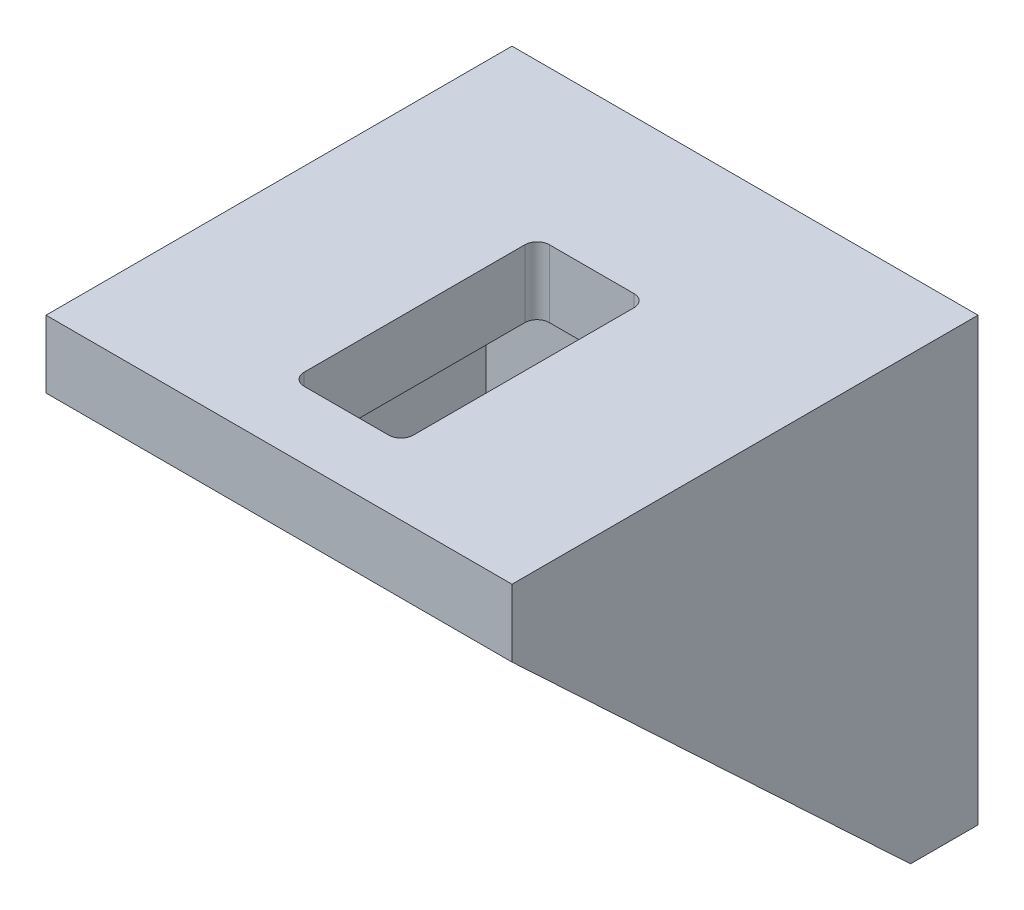
SolidWorks part; units mm, degrees
ref_plane "Front Plane" through (0, 0, 0) normal (0, 0, 1) x (1, 0, 0)
ref_plane "Top Plane" through (0, 0, 0) normal (0, 1, 0) x (1, 0, 0)
ref_plane "Right Plane" through (0, 0, 0) normal (1, 0, 0) x (0, 0, -1)
sketch "Sketch1" plane through (0, 0, 0) normal (0, 0, 1) x (1, 0, 0)
  line L1 (0, 0) -> (38, 0)
  line L2 (0, 0) -> (0, 36)
  line L3 (0, 36) -> (38, 36)
  line L4 (38, 0) -> (38, 36)
  dimension "D1" = 38
  dimension "D2" = 36
extrude "Boss-Extrude1" add sketch "Sketch1" along normal blind 5.5
sketch "Sketch5" plane through (0, 0, 5.5) normal (0, 0, 1) x (1, 0, 0)
  line L0 (38, 0) -> (38, 36) construction
  line L1 (0, 36) -> (38, 36)
  line L2 (0, 36) -> (0, 30.5)
  line L3 (0, 30.5) -> (38, 30.5)
  line L4 (38, 36) -> (38, 30.5)
  dimension "D1" = 5.5
extrude "Boss-Extrude5" add sketch "Sketch5" along normal blind 32.5
sketch "Sketch7" plane through (0, 0, 0) normal (-1, 0, 0) x (0, 0, 1)
  line L0 (5.5, 0) -> (38, 30.5)
  line L1 (38, 30.5) -> (5.5, 30.5)
  line L2 (5.5, 30.5) -> (5.5, 0)
extrude "Boss-Extrude6" add sketch "Sketch7" against normal blind 3.4
sketch "Sketch8" plane through (38, 0, 0) normal (1, 0, 0) x (0, 0, -1)
  line L0 (-5.5, 0) -> (-5.5, 30.5)
  line L1 (-5.5, 30.5) -> (-38, 30.5)
  line L2 (-38, 30.5) -> (-5.5, 0)
extrude "Boss-Extrude7" add sketch "Sketch8" against normal blind 3.4
sketch "Sketch9" plane through (0, 30.5, 0) normal (0, -1, 0) x (-1, 0, 0)
  line L1 (-23.45, -12.5) -> (-14.55, -12.5)
  line L2 (-23.45, -12.5) -> (-23.45, -32.5)
  line L3 (-23.45, -32.5) -> (-14.55, -32.5)
  line L4 (-14.55, -12.5) -> (-14.55, -32.5)
  line L6 (0, -5.5) -> (0, -38) construction
  line L8 (-3.4, -38) -> (-34.6, -38) construction
  dimension "D1" = 8.9
  dimension "D2" = 14.55
  dimension "D3" = 20
  dimension "D4" = 5.5
extrude "Cut-Extrude1" cut sketch "Sketch9" against normal through all
fillet "Fillet1" radius 1 4 edges at (23.45, 33.25, 32.5) (14.55, 33.25, 32.5) (23.45, 33.25, 12.5) (14.55, 33.25, 12.5)
sketch "Sketch12" plane through (0, 0, 0) normal (0, 0, -1) x (-1, 0, 0)
  line L0 (-38, 36) -> (0, 36) construction
  line L2 (0, 36) -> (0, 0) construction
  line L4 (-27.5, 21.1225) -> (-30.359, 21.1225)
  line L5 (-27.5, 21.1225) -> (-27.5, 10.4971)
  line L6 (-27.5, 10.4971) -> (-30.359, 10.4971)
  line L7 (-30.359, 21.1225) -> (-30.359, 10.4971)
  circle A1 centre (-18, 18) radius 10
  line M2 (0, 0) -> (0, 36)
  line M3 (0, 36) -> (-38, 36)
  line M4 (-38, 36) -> (-38, 0)
  line M5 (-38, 0) -> (0, 0)
  dimension "D1" = 20
  dimension "D2" = 18
  dimension "D3" = 18
  dimension "D4" = 9.5
extrude "Cut-Extrude3" cut sketch "Sketch12" against normal blind 3 flip side to cut contours A1 L5 L6 L7 L4 M5 M2 M3 M4 | A1 L4 L7 L6 L5 | L5 A1 region at (29.0204, 15.6478, 0) region at (27.7004, 18, 0) region at (19, 0.5235, 0)
sketch "Sketch19" plane through (0, 0, 0) normal (0, 0, -1) x (-1, 0, 0)
  line L0 (0, 36) -> (0, 0) construction
  line L1 (-8.4606, 21) -> (0, 21)
  line L2 (-8.4606, 21) -> (-8.4606, 15)
  line L3 (-8.4606, 15) -> (0, 15)
  line L4 (0, 21) -> (0, 15)
  arc A0 (-27.5, 14.8775) -> (-27.5, 21.1225) centre (-18, 18) ccw construction
  point P9 (-4.2303, 21)
  dimension "D1" = 6
  dimension "D2" = 3
extrude "Cut-Extrude4" cut sketch "Sketch19" against normal blind 3
